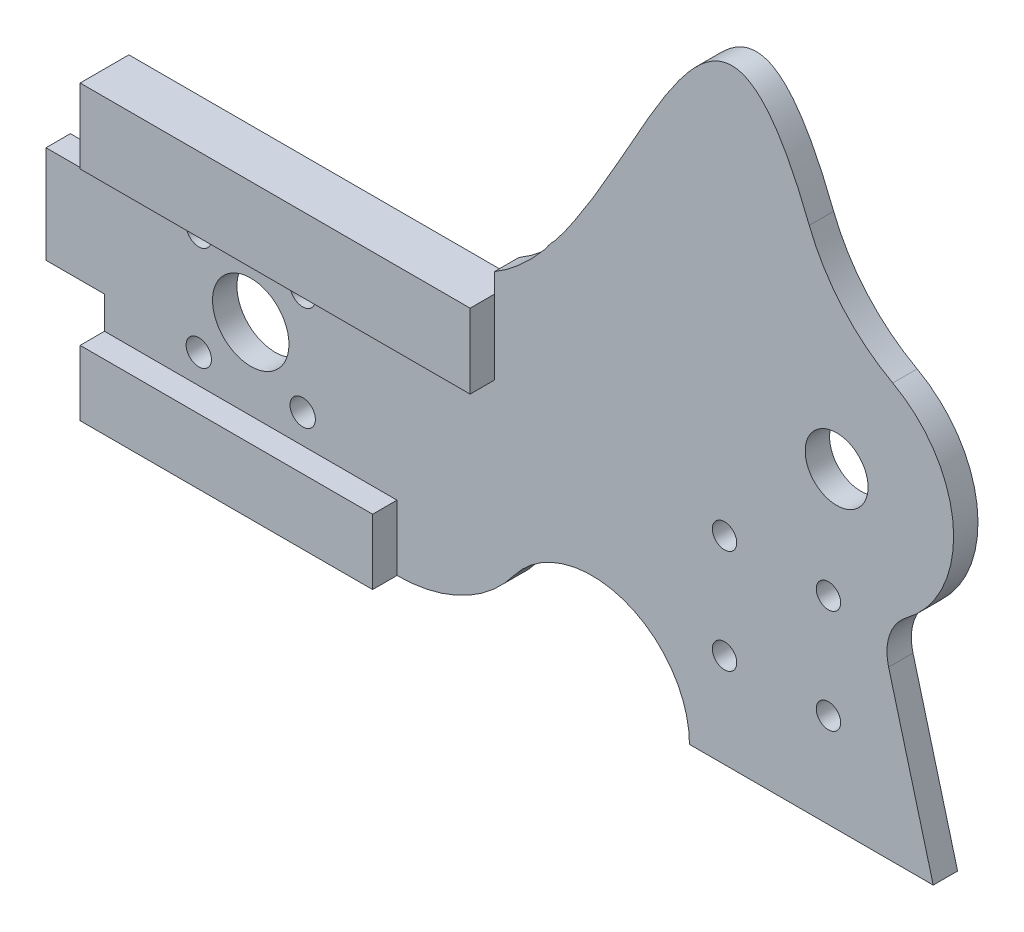
SolidWorks part; units mm, degrees
ref_plane "Front Plane" through (0, 0, 0) normal (0, 0, 1) x (1, 0, 0)
ref_plane "Top Plane" through (0, 0, 0) normal (0, 1, 0) x (1, 0, 0)
ref_plane "Right Plane" through (0, 0, 0) normal (1, 0, 0) x (0, 0, -1)
sketch "Sketch1" plane through (0, 0, 0) normal (0, 0, 1) x (1, 0, 0)
  line L0 (0, 0) -> (107.95, 0)
  line L3 (0, 38.1) -> (0, 25.4)
  line L4 (95.3675, 55.88) -> (0, 38.1)
  line L5 (0, 19.05) -> (100.2273, 19.05) construction
  line L6 (19.05, 19.05) -> (19.05, 28.62) construction
  line L7 (19.05, 19.05) -> (25.817, 25.817) construction
  line L8 (107.95, 0) -> (100.9363, 26.1756)
  line L10 (0, 12.7) -> (0, 0)
  line L11 (0, 25.4) -> (-7.62, 25.4)
  line L13 (0, 12.7) -> (-7.62, 12.7)
  line L14 (-7.62, 25.4) -> (-7.62, 12.7)
  line L15 (100.9363, 26.1756) -> (100.8688, 26.4276)
  arc A0 (100.8688, 26.4276) -> (95.3675, 55.88) centre (95.3675, 40.64) ccw
  circle A1 centre (95.3675, 40.64) radius 4.0957
  circle A2 centre (19.05, 19.05) radius 9.57 construction
  circle A3 centre (25.817, 25.817) radius 1.651
  circle A4 centre (25.817, 12.283) radius 1.651
  circle A5 centre (12.283, 12.283) radius 1.651
  circle A6 centre (12.283, 25.817) radius 1.651
  point P26 (19.05, 19.05)
  dimension "D1" = 8.1915
  dimension "D5" = 15.24
  dimension "D4" = 19.14
  dimension "D7" = 3.302
  dimension "D11" = 97.0107
  dimension "D2" = 38.1
  dimension "D3" = 40.64
  dimension "D6" = 107.95
  dimension "D8" = 45
  dimension "D9" = 4
  dimension "D10" = 19.05
  dimension "D12" = 75
  dimension "D14" = 12.7
  dimension "D15" = 12.7
  dimension "D16" = 7.62
extrude "Boss-Extrude1" add sketch "Sketch1" along normal blind 3.175
sketch "Sketch2" plane through (0, 0, 3.175) normal (0, 0, 1) x (1, 0, 0)
  circle A0 centre (95.3675, 40.64) radius 38.1 construction
sketch "Sketch6" plane through (0, 0, 3.175) normal (0, 0, 1) x (1, 0, 0)
  line L0 (0, 0) -> (107.95, 0) construction
  line L1 (50.8, 0) -> (76.2, 0)
  arc A0 (76.2, 0) -> (50.8, 0) centre (63.5, 0) ccw
  dimension "D1" = 25.4
  dimension "D2" = 31.75
extrude "Cut-Extrude2" cut sketch "Sketch6" against normal blind 6.35
sketch "Sketch7" plane through (0, 0, 3.175) normal (0, 0, 1) x (1, 0, 0)
  line L0 (12.283, 25.817) -> (25.817, 12.283) construction
  line L1 (12.283, 12.283) -> (25.817, 25.817) construction
  line L2 (12.283, 25.817) -> (78.4839, 25.817) construction
  line L3 (11.7326, 12.283) -> (12.283, 12.283) construction
  circle A0 centre (19.05, 19.05) radius 4.9784
  circle A4 centre (80.7666, 12.283) radius 1.5875
  circle A5 centre (94.2997, 12.283) radius 1.5875
  circle A6 centre (80.7666, 25.817) radius 1.5875
  circle A7 centre (94.2997, 25.817) radius 1.5875
  dimension "D1" = 9.9568
  dimension "D2" = 3.175
  dimension "D3" = 13.5331
extrude "Cut-Extrude3" cut sketch "Sketch7" against normal through all
fillet "Fillet1" radius 6.35 1 edges at (100.8688, 26.4276, 1.5875)
sketch "Sketch8" plane through (0, 0, 3.175) normal (0, 0, 1) x (1, 0, 0)
  line L1 (0, 38.1) -> (50.8, 38.1)
  line L2 (0, 38.1) -> (0, 50.8)
  line L3 (0, 50.8) -> (50.8, 50.8)
  line L4 (50.8, 38.1) -> (50.8, 50.8)
  dimension "D1" = 50.8
  dimension "D2" = 12.7
extrude "Cut-Extrude4" cut sketch "Sketch8" against normal blind 50.8
sketch "Sketch9" plane through (0, 0, 3.175) normal (0, 0, 1) x (1, 0, 0)
  line L3 (50.8, 40.64) -> (57.15, 40.64)
  line L5 (57.15, 40.64) -> (50.8, 40.64)
  line L6 (57.15, 40.64) -> (57.15, 50.8)
  line L7 (57.15, 50.8) -> (50.8, 50.8)
  line L8 (50.8, 40.64) -> (50.8, 50.8)
  line L9 (0, 38.1) -> (50.8, 38.1) construction
  line M8 (50.8, 47.571) -> (50.8, 38.1)
  line M21 (95.3675, 55.88) -> (50.8, 47.571)
  dimension "D1" = 10.16
  dimension "D2" = 2.54
  dimension "D3" = 6.35
extrude "Cut-Extrude5" cut sketch "Sketch9" against normal blind 19.304 contours L3 L6 M21 M8 region at (54.0583, 44.4092, 3.175)
fillet "Fillet6" radius 6.35 1 edges at (57.15, 40.64, 1.5875)
fillet "Fillet7" radius 6.35 1 edges at (57.15, 48.7549, 1.5875)
fillet "Fillet8" radius 19.05 1 edges at (50.8, 0, 1.5875)
sketch "Sketch12" plane through (0, 0, 3.175) normal (0, 0, 1) x (1, 0, 0)
  line L0 (107.95, 0) -> (146.812, 0) construction
  line L1 (8.0257, 45.4128) -> (80.6683, 75.7903) construction
  line L2 (95.3675, 40.64) -> (80.6683, 75.7903) construction
  line L3 (80.6683, 75.7903) -> (79.4434, 78.7195) construction
  line L4 (50.8, 40.64) -> (85.0271, 40.64)
  line L5 (85.0271, 40.64) -> (95.3675, 55.88)
  arc A0 (61.8128, 49.6242) -> (56.8883, 45.1859) centre (62.9766, 43.3817) ccw construction
  circle A1 centre (19.05, 19.05) radius 28.575 construction
  circle A2 centre (95.3675, 40.64) radius 38.1 construction
  circle A3 centre (80.6683, 75.7903) radius 3.175 construction
  spline S0 degree 3 poles (50.8, 40.64) (70.7778, 52.1788) (78.5943, 111.5434) (95.3675, 55.88) knots 0 0 0 0 1 1 1 1
  dimension "D2" = 6.35
  dimension "D1" = 38.862
extrude "Boss-Extrude2" add sketch "Sketch12" against normal blind 3.175
fillet "Fillet9" radius 24.13 1 edges at (95.3675, 55.88, 1.5875)
sketch "Sketch13" plane through (0, 0, 0) normal (0, 0, -1) x (-1, 0, 0)
  line L0 (0, 38.1) -> (0, 25.4) construction
  line L1 (-50.8, 38.1) -> (0, 38.1)
  line L2 (-50.8, 38.1) -> (-50.8, 28.4023)
  line L3 (-50.8, 28.4023) -> (0, 28.4023)
  line L4 (0, 38.1) -> (0, 28.4023)
  line L5 (0, 12.7) -> (0, 0) construction
  line L6 (0, 8.5046) -> (-38.1, 8.5046)
  line L7 (0, 8.5046) -> (0, 0)
  line L8 (0, 0) -> (-38.1, 0)
  line L9 (-38.1, 8.5046) -> (-38.1, 0)
extrude "Boss-Extrude3" add sketch "Sketch13" against normal blind 6.35
